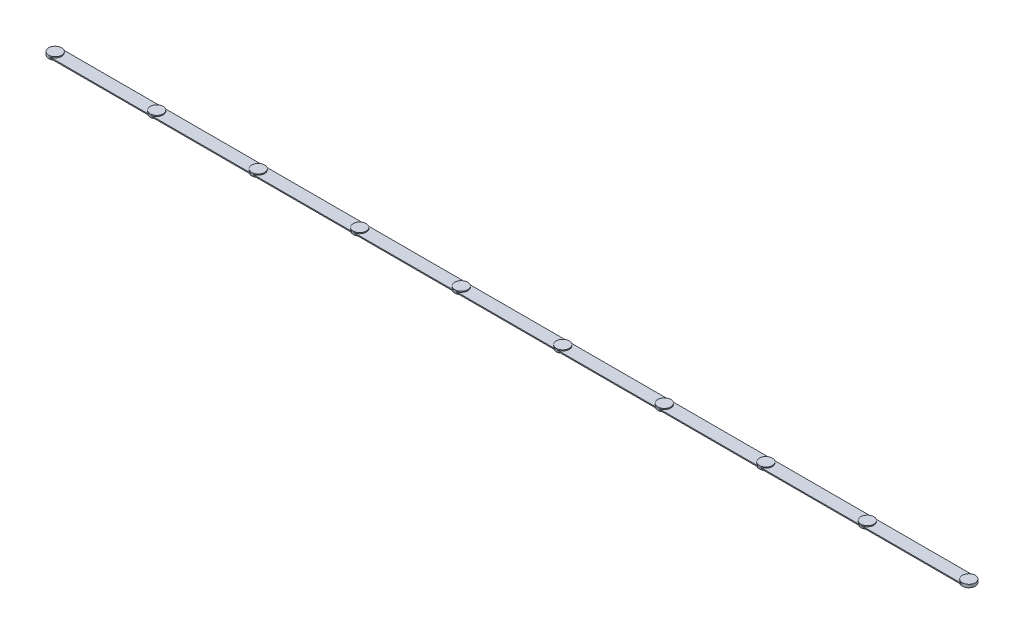
SolidWorks part; units mm, degrees
material "Natural Rubber"
ref_plane "Front Plane" through (0, 0, 0) normal (0, 0, 1) x (1, 0, 0)
ref_plane "Top Plane" through (0, 0, 0) normal (0, 1, 0) x (1, 0, 0)
ref_plane "Right Plane" through (0, 0, 0) normal (1, 0, 0) x (0, 0, -1)
sketch "Sketch1" plane through (0, 0, 0) normal (0, 1, 0) x (1, 0, 0)
  line L1 (0, -12.75) -> (200, -12.75)
  line L3 (0, 12.75) -> (200, 12.75)
  arc A0 (0, 12.75) -> (0, -12.75) centre (0, 0) ccw
  arc A1 (200, -12.75) -> (200, 12.75) centre (200, 0) ccw
  dimension "D1" = 25.5
  dimension "D2" = 200
extrude "Boss-Extrude1" add sketch "Sketch1" along normal blind 2
sketch "Sketch2" plane through (0, 2, 0) normal (0, 1, 0) x (1, 0, 0)
  circle A0 centre (0, 0) radius 12.75
  circle A1 centre (200, 0) radius 12.75
extrude "Boss-Extrude2" add sketch "Sketch2" along normal blind 2
sketch "Sketch3" plane through (0, 0, 0) normal (0, -1, 0) x (1, 0, 0)
  circle A0 centre (200, 0) radius 12.75
extrude "Cut-Extrude1" cut sketch "Sketch3" against normal blind 45
sketch "Sketch5" plane through (0, 0, 0) normal (0, -1, 0) x (1, 0, 0)
  circle A0 centre (0, 0) radius 12.75
extrude "Boss-Extrude3" add sketch "Sketch5" along normal blind 2
pattern_linear "LPattern3" count 10 spacing 200 along (1, 0, 0) of bodies 124
sketch "Sketch6" plane through (0, 0, 0) normal (0, -1, 0) x (1, 0, 0)
  line L0 (2000, -12.75) -> (1800, -12.75) construction
  line L1 (1800, 12.75) -> (2000, 12.75)
  line L3 (1800, -12.75) -> (2000, -12.75)
  line L4 (2000, 12.75) -> (2000, -12.75)
  arc A0 (1800, -12.75) -> (1800, 12.75) centre (1800, 0) ccw
  arc A1 (2000, 12.75) -> (2000, -12.75) centre (2000, 0) ccw construction
extrude "Cut-Extrude3" cut sketch "Sketch6" against normal blind 5
